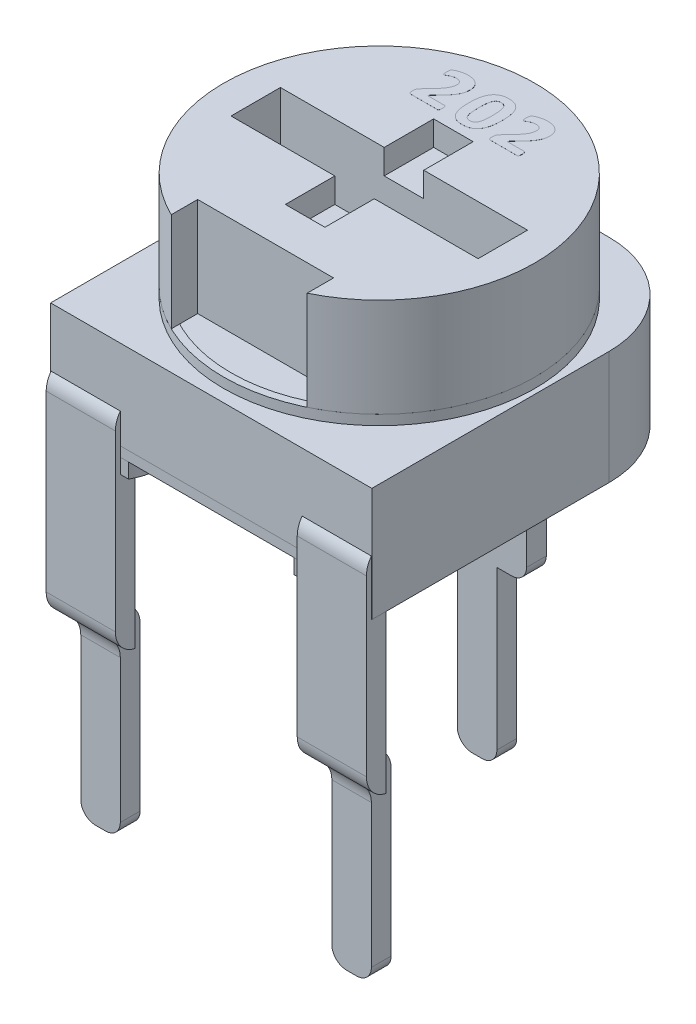
SolidWorks part; units mm, degrees
material "ABS"
ref_plane "Front Plane" through (0, 0, 0) normal (0, 0, 1) x (1, 0, 0)
ref_plane "Top Plane" through (0, 0, 0) normal (0, 1, 0) x (1, 0, 0)
ref_plane "Right Plane" through (0, 0, 0) normal (1, 0, 0) x (0, 0, -1)
sketch "Sketch1" plane through (0, 0, 0) normal (0, 1, 0) x (1, 0, 0)
  line L0 (0, 3.15) -> (0, -3.15) construction
  line L1 (0, 3.15) -> (0, 3.4) construction
  line L2 (0, -3.15) -> (0, -3.4) construction
  line L3 (-3.15, 0) -> (3.15, 0) construction
  line L4 (3.15, 0) -> (3.25, 0) construction
  line L5 (-3.15, 0) -> (-3.25, 0) construction
  line L6 (-3.25, -3.4) -> (3.25, -3.4)
  line L7 (-3.25, -3.4) -> (-3.25, 3.4)
  line L8 (-3.25, 3.4) -> (3.25, 3.4)
  line L9 (3.25, 3.4) -> (3.25, -3.4)
  circle A0 centre (0, 0) radius 3.15 construction
  dimension "D1" = 6.3
  dimension "D2" = 6.8
  dimension "D3" = 6.5
extrude "Boss-Extrude1" add sketch "Sketch1" along normal blind 2.3
sketch "Sketch2" plane through (0, 2.3, 0) normal (0, 1, 0) x (1, 0, 0)
  circle A0 centre (0, 0) radius 3.15 construction
  circle A1 centre (0, 0) radius 3.15
extrude "Boss-Extrude2" add sketch "Sketch2" along normal blind 0.2
fillet "Fillet1" radius 2 2 edges at (3.25, 1.15, -3.4) (-3.25, 1.15, -3.4)
sketch "Sketch3" plane through (0, 0, 0) normal (0, -1, 0) x (1, 0, 0)
  line L0 (0, 0) -> (0, -2.5) construction
  line L1 (-1.75, -2.5) -> (1.75, -2.5)
  line L6 (-2.25, -2) -> (-2.25, 2)
  line L7 (2.25, -2) -> (2.25, 2)
  line L8 (-2.25, 2) -> (-3, 2)
  line L9 (-3, 2) -> (-3, 3.4)
  line L10 (-3.25, 3.4) -> (3.25, 3.4) construction
  line L11 (2.25, 2) -> (3, 2)
  line L12 (3, 2) -> (3, 3.4)
  line L13 (3, 3.4) -> (-3, 3.4)
  line L14 (0, 0) -> (0, 3.4) construction
  arc A0 (-1.75, -2.5) -> (-2.25, -2) centre (-1.75, -2) cw
  arc A1 (1.75, -2.5) -> (2.25, -2) centre (1.75, -2) ccw
  point P20 (2.25, -2.5)
  dimension "D6" = 0.5
  dimension "D1" = 4.5
  dimension "D2" = 2.5
  dimension "D3" = 4.5
  dimension "D4" = 1.4
  dimension "D5" = 6
extrude "Cut-Extrude1" cut sketch "Sketch3" against normal blind 0.5
sketch "Sketch4" plane through (0, 0.5, 0) normal (0, -1, 0) x (1, 0, 0)
  line L8 (-3, 2) -> (-2.25, 2)
  line L9 (-2.25, 2) -> (-2.25, -2)
  line L10 (-1.75, -2.5) -> (1.75, -2.5)
  line L11 (2.25, -2) -> (2.25, 2)
  line L12 (2.25, 2) -> (3, 2)
  line L13 (3, 2) -> (3, 3.4)
  line L14 (3, 3.4) -> (-3, 3.4)
  line L15 (-3, 3.4) -> (-3, 2)
  line L16 (-3, 2) -> (-2.25, 2)
  line L17 (-2.25, 2) -> (-2.25, -2)
  line L18 (-1.75, -2.5) -> (1.75, -2.5)
  line L19 (2.25, -2) -> (2.25, 2)
  line L20 (2.25, 2) -> (3, 2)
  line L21 (3, 2) -> (3, 3.4)
  line L22 (3, 3.4) -> (-3, 3.4)
  line L23 (-3, 3.4) -> (-3, 2)
  arc A2 (-2.25, -2) -> (-1.75, -2.5) centre (-1.75, -2) ccw
  arc A3 (1.75, -2.5) -> (2.25, -2) centre (1.75, -2) ccw
  arc A4 (-2.25, -2) -> (-1.75, -2.5) centre (-1.75, -2) ccw
  arc A5 (1.75, -2.5) -> (2.25, -2) centre (1.75, -2) ccw
  dimension "D1" = 0
extrude "Boss-Extrude3" add sketch "Sketch4" along normal blind 0.2 separate body
sketch "Sketch5" plane through (0, 0.3, 0) normal (0, -1, 0) x (1, 0, 0)
  line L0 (0, 3.4) -> (0, 2.9) construction
  line L1 (3, 3.4) -> (-3, 3.4) construction
  line L2 (0, 2.9) -> (0, -2.18) construction
  line L3 (-2.54, 2.9) -> (2.54, 2.9) construction
  circle A0 centre (2.54, 2.9) radius 1
  circle A1 centre (-2.54, 2.9) radius 1
  circle A2 centre (0, -2.18) radius 1
  dimension "D2" = 5.08
  dimension "D4" = 2
  dimension "D1" = 0.5
  dimension "D3" = 5.08
extrude "Boss-Extrude4" add sketch "Sketch5" along normal up to surface (0.3 mm away) up to face at (0, 0, 0.1228)
sketch "Sketch6" plane through (0, 0.3, 0) normal (0, 1, 0) x (1, 0, 0)
  line L0 (-3.25, -3.4) -> (-3.25, -1)
  line L1 (-3.25, 1.4) -> (-3.25, -3.4) construction
  line L2 (-3.25, -1) -> (-4.35, -1)
  line L3 (-4.35, -1) -> (-4.35, -4.5)
  line L4 (-4.35, -4.5) -> (4.35, -4.5)
  line L5 (4.35, -4.5) -> (4.35, -1)
  line L6 (4.35, -1) -> (3.25, -1)
  line L7 (3.25, -3.4) -> (3.25, 1.4) construction
  line L8 (-3.25, -3.4) -> (3.25, -3.4)
  line L9 (3.25, -3.4) -> (3.25, -1)
  line L10 (0, 0) -> (0, -3.4) construction
  line L11 (0, -3.4) -> (0, -4.5) construction
  dimension "D1" = 3.5
extrude "Cut-Extrude2" cut sketch "Sketch6" against normal up to surface (0.3 mm away) up to face at (0, 0, -0.817)
sketch "Sketch8" plane through (0, 0.3, 0) normal (0, -1, 0) x (1, 0, 0)
  line L1 (-0.4, -1.98) -> (0.4, -1.98)
  line L2 (-0.4, -1.98) -> (-0.4, -2.38)
  line L3 (-0.4, -2.38) -> (0.4, -2.38)
  line L4 (0.4, -1.98) -> (0.4, -2.38)
  line L5 (-0.4, -1.98) -> (0.4, -2.38) construction
  line L6 (-0.4, -2.38) -> (0.4, -1.98) construction
  line L7 (-2.94, 3.1) -> (-2.14, 3.1)
  line L8 (-2.94, 3.1) -> (-2.94, 2.7)
  line L9 (-2.94, 2.7) -> (-2.14, 2.7)
  line L10 (-2.14, 3.1) -> (-2.14, 2.7)
  line L11 (-2.94, 3.1) -> (-2.14, 2.7) construction
  line L12 (-2.94, 2.7) -> (-2.14, 3.1) construction
  line L13 (2.94, 3.1) -> (2.14, 3.1)
  line L14 (2.94, 3.1) -> (2.94, 2.7)
  line L15 (2.94, 2.7) -> (2.14, 2.7)
  line L16 (2.14, 3.1) -> (2.14, 2.7)
  line L17 (2.94, 3.1) -> (2.14, 2.7) construction
  line L18 (2.94, 2.7) -> (2.14, 3.1) construction
  point P0 (0, -2.18)
  point P5 (-2.54, 2.9)
  point P11 (2.54, 2.9)
  dimension "D1" = 0.4
  dimension "D2" = 0.8
extrude "Boss-Extrude5" add sketch "Sketch8" along normal blind 7
sketch "Sketch9" plane through (0, 0.3, 0) normal (0, -1, 0) x (1, 0, 0)
  line L4 (0, -1.98) -> (0, -2.38) construction
  line L5 (0.4, -1.98) -> (-0.4, -1.98) construction
  line L6 (-0.4, -2.38) -> (0.4, -2.38) construction
  line L8 (-1, -1.98) -> (1, -1.98)
  line L9 (-1, -1.98) -> (-1, -2.38)
  line L10 (-1, -2.38) -> (1, -2.38)
  line L11 (1, -1.98) -> (1, -2.38)
  line L12 (-1, -1.98) -> (1, -2.38) construction
  line L13 (-1, -2.38) -> (1, -1.98) construction
  point P14 (0, -2.18)
  dimension "D1" = 2
extrude "Boss-Extrude6" add sketch "Sketch9" along normal blind 3.5
sketch "Sketch10" plane through (0, 0.3, 0) normal (0, -1, 0) x (1, 0, 0)
  line L0 (-2.54, 3.1) -> (-2.54, 3.5) construction
  line L1 (-2.14, 3.1) -> (-2.94, 3.1) construction
  line L2 (2.54, 3.1) -> (2.54, 3.5) construction
  line L3 (2.94, 3.1) -> (2.14, 3.1) construction
  line L4 (-2.94, 3.1) -> (-2.94, 2.7) construction
  line L5 (-3.24, 3.5) -> (-1.84, 3.5)
  line L6 (-3.24, 3.5) -> (-3.24, 3.1)
  line L7 (-3.24, 3.1) -> (-1.84, 3.1)
  line L8 (-1.84, 3.5) -> (-1.84, 3.1)
  line L10 (1.84, 3.5) -> (3.24, 3.5)
  line L11 (1.84, 3.5) -> (1.84, 3.1)
  line L12 (1.84, 3.1) -> (3.24, 3.1)
  line L13 (3.24, 3.5) -> (3.24, 3.1)
  dimension "D1" = 1.4
extrude "Boss-Extrude7" add sketch "Sketch10" along normal blind 3.5 and the other way blind 1
fillet "Fillet2" radius 0.5 2 edges at (2.54, 1.3, 3.5) (-2.54, 1.3, 3.5)
sketch "Sketch11" plane through (0, 0, 0) normal (1, 0, 0) x (0, 0, -1)
  line L0 (-3.4, 0) -> (1.4, 0) construction
  line L1 (-3.1, -2.8) -> (-2.7, -2.8)
  line L2 (-3.1, -2.8) -> (-3.1, 0)
  line L3 (-3.1, 0) -> (-2.7, 0)
  line L4 (-2.7, -2.8) -> (-2.7, 0)
  line L5 (-2.7, -6.7) -> (-2.7, 0.3) construction
  line L6 (-3.1, -2.8) -> (-3.1, -3.2) construction
extrude "Cut-Extrude3" cut sketch "Sketch11" against normal through all both and the other way through all
fillet "Fillet3" radius 0.5 4 edges at (-2.54, -2.8, 3.1) (2.54, -2.8, 3.1) (-2.54, -3.2, 3.5) (2.54, -3.2, 3.5)
fillet "Fillet4" radius 0.5 4 edges at (2.54, -2.8, 2.7) (-2.54, -2.8, 2.7) (2.54, -3.2, 3.1) (-2.54, -3.2, 3.1)
fillet "Fillet5" radius 0.3 12 edges at (-1, -3.2, -2.18) (1, -3.2, -2.18) (-0.4, -6.7, -2.18) (0.4, -6.7, -2.18) (2.14, -6.7, 2.9) (2.94, -6.7, 2.9) (-2.94, -6.7, 2.9) (-2.14, -6.7, 2.9) (-2.14, -2.7551, 3.1) (-2.94, -2.7551, 3.1) (2.14, -2.7551, 3.1) (2.94, -2.7551, 3.1)
sketch "Sketch12" plane through (0, 0.3, 0) normal (0, -1, 0) x (1, 0, 0)
  circle A0 centre (0, 0) radius 2
  circle A1 centre (0, 0) radius 1.5
  dimension "D1" = 4
  dimension "D2" = 3
extrude "Boss-Extrude8" add sketch "Sketch12" along normal blind 0.15
sketch "Sketch15" plane through (0, 2.5, 0) normal (0, 1, 0) x (1, 0, 0)
  circle A0 centre (0, 0) radius 3
  dimension "D1" = 6
extrude "Cut-Extrude4" cut sketch "Sketch15" against normal blind 0.5
sketch "Sketch14" plane through (0, 2.5, 0) normal (0, 1, 0) x (1, 0, 0)
  circle A1 centre (0, 0) radius 3.15
  circle A2 centre (0, 0) radius 3.15
  dimension "D1" = 0
extrude "Boss-Extrude9" add sketch "Sketch14" along normal blind 2 separate body
sketch "Set Angle of Knob" plane through (0, 4.5, 0) normal (0, 1, 0) x (1, 0, 0)
  line L0 (0, 0) -> (0, -3.15) construction
  line L1 (-2.5, 0) -> (2.5, 0) construction
  line L2 (-2.5, 0.5) -> (-2.5, -0.5)
  line L3 (2.5, 0.5) -> (2.5, -0.5)
  line L4 (-2.5, 0.5) -> (-0.4, 0.5)
  line L5 (-2.5, -0.5) -> (-0.4, -0.5)
  line L6 (0, 0) -> (0, -1.5) construction
  line L7 (0, 0) -> (0, 1.5) construction
  line L8 (0, 1.5) -> (0, 3.15) construction
  line L9 (0.4, 1.5) -> (-0.4, 1.5)
  line L10 (0.4, 1.5) -> (0.4, 0.5)
  line L11 (-0.4, 1.5) -> (-0.4, 0.5)
  line L12 (0.4, 0.5) -> (2.5, 0.5)
  line L13 (-0.4, -1.5) -> (0.4, -1.5)
  line L14 (-0.4, -1.5) -> (-0.4, -0.5)
  line L15 (0.4, -1.5) -> (0.4, -0.5)
  line L16 (0.4, -0.5) -> (2.5, -0.5)
  line L17 (0, -1.5) -> (0, -2.3) construction
  line L18 (-1.375, -2.3) -> (1.375, -2.3)
  line L19 (-1.375, -2.3) -> (-1.375, -3.8)
  line L20 (1.375, -2.3) -> (1.375, -3.8)
  line L21 (-1.375, -3.8) -> (1.375, -3.8)
  line L22 (-1, 0.25) -> (1, 0.25) construction
  line L23 (-1, 0.25) -> (-1, -0.25) construction
  line L24 (-1, -0.25) -> (1, -0.25) construction
  line L25 (1, -0.25) -> (1, 0.25) construction
  circle A0 centre (0, 0) radius 3.15 construction
  circle A1 centre (0, 0) radius 3.15 construction
  point P32 (0, 0.25)
  dimension "D1" = 1
  dimension "D2" = 0.8
  dimension "D3" = 1.5
  dimension "D4" = 5
  dimension "D5" = 90
  dimension "D6" = 2.75
  dimension "D7" = 1.5
  dimension "D8" = 1.8
  dimension "D9" = 0.25
  dimension "D10" = 0.25
  dimension "D11" = 2
extrude "TURN KNOB" cut sketch "Set Angle of Knob" against normal blind 2.3
sketch "Sketch17" plane through (0, 2, 0) normal (0, 1, 0) x (1, 0, 0)
  line L0 (-0.4, -1.5) -> (0.4, -1.5)
  line L1 (0.4, -1.5) -> (0.4, -0.5)
  line L2 (0.4, 1.5) -> (-0.4, 1.5)
  line L3 (-0.4, 1.5) -> (-0.4, 0.5)
  line L4 (-0.4, 0.5) -> (0.4, 0.5)
  line L5 (-0.4, -0.5) -> (0.4, -0.5)
  line L6 (-0.4, -0.5) -> (-0.4, -1.5)
  line L7 (0.4, 0.5) -> (0.4, 1.5)
extrude "Boss-Extrude10" add sketch "Sketch17" along normal blind 2
sketch "Sketch20" plane through (0, 2, 0) normal (0, 1, 0) x (1, 0, 0)
  line L0 (-1, 0.25) -> (1, 0.25) construction
  line L1 (-1, 0.25) -> (1, 0.25)
  line L2 (-1, -0.25) -> (1, -0.25) construction
  line L3 (-1, -0.25) -> (1, -0.25)
  line L4 (-1, 0.25) -> (-1, -0.25) construction
  line L5 (-1, 0.25) -> (-1, -0.25)
  line L6 (1, -0.25) -> (1, 0.25) construction
  line L7 (1, -0.25) -> (1, 0.25)
extrude "Cut-Extrude6" cut sketch "Sketch20" against normal blind 0.5
fillet "Fillet6" radius 0.2 2 edges at (1, 2, 0) (-1, 2, 0)
sketch "See Code in Properties" plane through (0, 4.5, 0) normal (0, 1, 0) x (1, 0, 0)
  line L0 (0, 1.5) -> (0, 1.7) construction
  line L1 (0.4, 1.5) -> (-0.4, 1.5) construction
  line L2 (0, 1.5) -> (0, 3.15) construction
  line L3 (-1.5, 1.7) -> (1.5, 1.7) construction
  text T0 "202" font "Calibri" height 0.9
  dimension "D1" = 0.2
  dimension "D2" = 3
extrude "Code Number" add sketch "See Code in Properties" along normal blind 0.001
